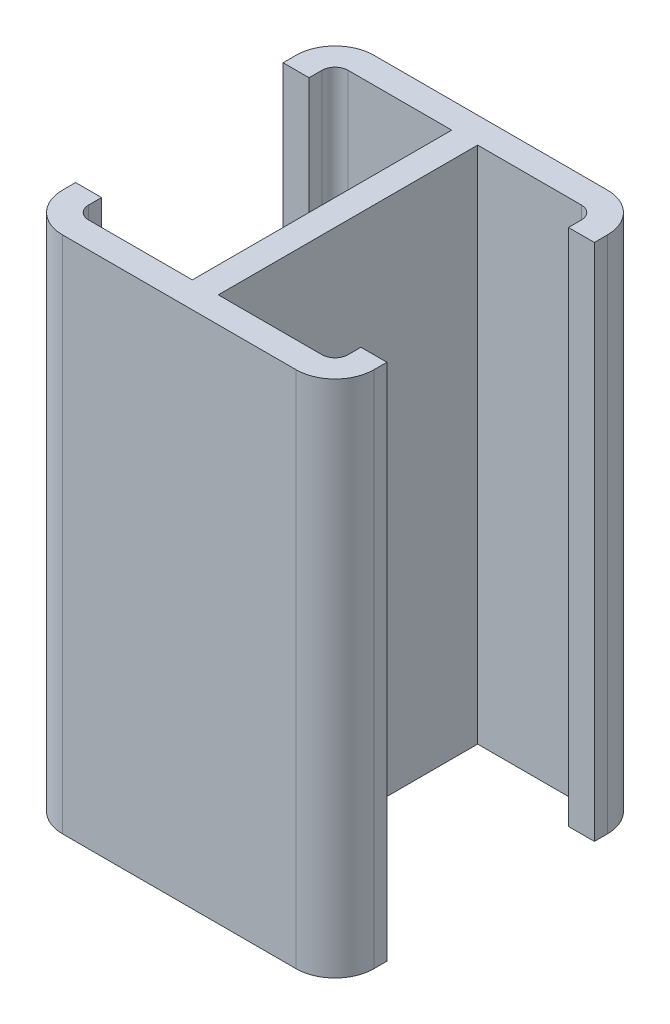
SolidWorks part; units mm, degrees
ref_plane "正面" through (0, 0, 0) normal (0, 0, 1) x (1, 0, 0)
ref_plane "平面" through (0, 0, 0) normal (0, 1, 0) x (1, 0, 0)
ref_plane "右側面" through (0, 0, 0) normal (1, 0, 0) x (0, 0, -1)
sketch "ｽｹｯﾁ1" plane through (0, 0, 0) normal (0, 1, 0) x (1, 0, 0)
  line L0 (0, 0) -> (0, -60)
  line L1 (0, -60) -> (45, -60)
  line L2 (60, -45) -> (60, -40)
  line L3 (60, -40) -> (50, -40)
  line L4 (50, -40) -> (50, -45)
  line L5 (45, -50) -> (5, -50)
  line L6 (5, -50) -> (5, 0)
  line L7 (5, 0) -> (0, 0)
  arc A0 (60, -45) -> (45, -60) centre (45, -45) cw
  arc A1 (50, -45) -> (45, -50) centre (45, -45) cw
  point P11 (60, -60)
  point P14 (50, -50)
  dimension "D7" = 15
  dimension "D8" = 5
  dimension "D1" = 60
  dimension "D2" = 60
  dimension "D3" = 20
  dimension "D4" = 10
  dimension "D5" = 10
  dimension "D6" = 5
extrude "ﾎﾞｽ - 押し出し1" add sketch "ｽｹｯﾁ1" along normal blind 200
mirror "ﾐﾗｰ1" about plane through (0, 200, 0) normal (1, 0, 0) of bodies 101
mirror "ﾐﾗｰ2" about plane through (5, 200, 0) normal (0, 0, 1) of bodies 104
equation "\"C\"= 20"
equation "\"D3@ｽｹｯﾁ1\"=\"C\""
equation "\"B\" = 10"
equation "\"D4@ｽｹｯﾁ1\"=\"B\""
equation "\"D5@ｽｹｯﾁ1\"=\"B\""
equation "\"A\" = 10"
equation "\"D6@ｽｹｯﾁ1\"=\"A\"/2"
equation "\"D8@ｽｹｯﾁ1\"= \"B\"/2"
equation "\"D7@ｽｹｯﾁ1\"= \"B\"/2*3"
